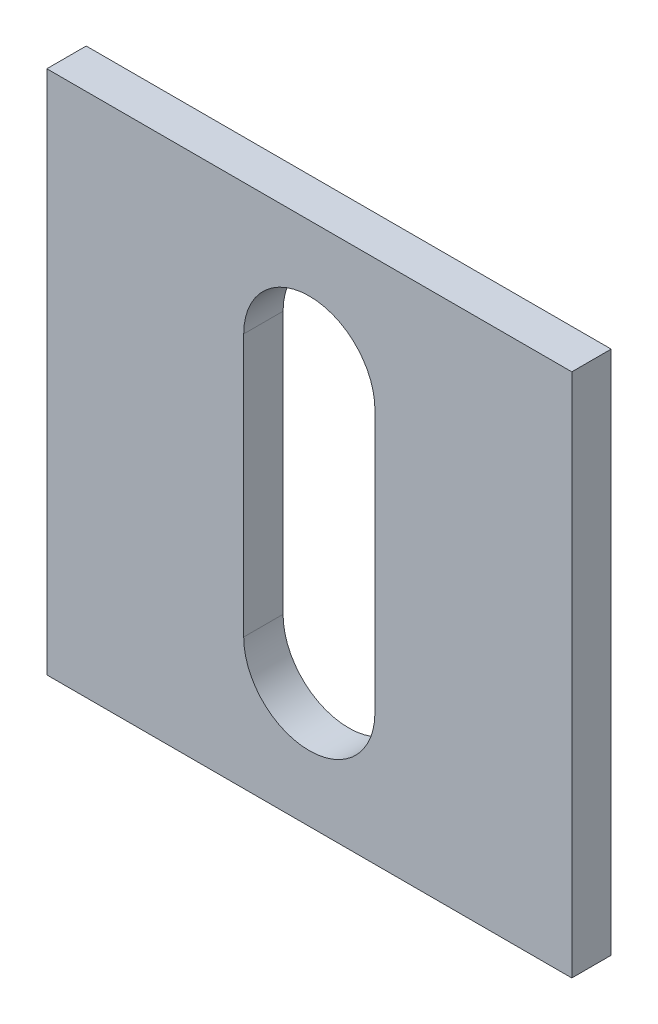
SolidWorks part; units mm, degrees
material "ABS"
ref_plane "Front Plane" through (0, 0, 0) normal (0, 0, 1) x (1, 0, 0)
ref_plane "Top Plane" through (0, 0, 0) normal (0, 1, 0) x (1, 0, 0)
ref_plane "Right Plane" through (0, 0, 0) normal (1, 0, 0) x (0, 0, -1)
sketch "Sketch1" plane through (0, 0, 0) normal (0, 0, 1) x (1, 0, 0)
  line L0 (20, 40) -> (20, 20) construction
  line L1 (0, 0) -> (40, 0)
  line L2 (0, 0) -> (0, 40)
  line L3 (0, 40) -> (40, 40)
  line L4 (40, 0) -> (40, 40)
  line L5 (20, 20) -> (20, 0) construction
  line L6 (20, 30) -> (20, 10) construction
  line L7 (25, 30) -> (25, 10)
  line L8 (15, 30) -> (15, 10)
  arc A0 (25, 30) -> (15, 30) centre (20, 30) ccw
  arc A1 (15, 10) -> (25, 10) centre (20, 10) ccw
  point P10 (20, 20)
  dimension "D3" = 5
  dimension "D1" = 40
  dimension "D2" = 40
extrude "Boss-Extrude1" add sketch "Sketch1" along normal blind 3
